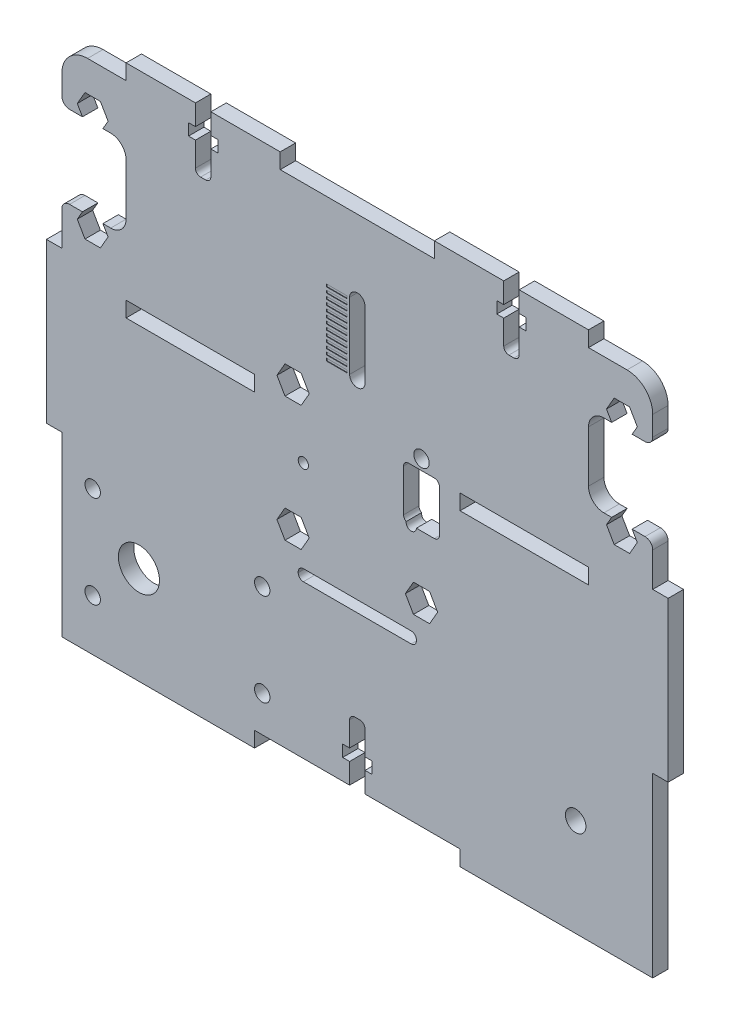
SolidWorks part; units mm, degrees
other "Marcação1"
sketch "Esboço7" plane through (-68, 31.5, 3) normal (-0.6758, 0.2828, 0.6807) x (0.7271, 0.1043, 0.6785)
sketch "Esboço8" plane through (-68, 31.5, 3) normal (-0.6758, 0.2828, 0.6807) x (0.7271, 0.1043, 0.6785)
sketch "Esboço9" plane through (-68, 31.5, 3) normal (-0.6758, 0.2828, 0.6807) x (0.7271, 0.1043, 0.6785)
sketch "Esboço10" plane through (-68, 31.5, 3) normal (-0.6758, 0.2828, 0.6807) x (0.7271, 0.1043, 0.6785)
sketch "Esboço11" plane through (-68, 36.25, 3) normal (-0.6758, 0.2828, 0.6807) x (0.7271, 0.1043, 0.6785)
sketch "Esboço13" plane through (-68, 36.25, 3) normal (-0.6758, 0.2828, 0.6807) x (0.7271, 0.1043, 0.6785)
sketch "Esboço15" plane through (-68, 36.25, 3) normal (-0.6758, 0.2828, 0.6807) x (0.7271, 0.1043, 0.6785)
sketch "Esboço19" plane through (-68, 66.25, 3) normal (-0.6758, 0.2828, 0.6807) x (0.7271, 0.1043, 0.6785)
sketch "Esboço22" plane through (-68, 95.5577, 3) normal (-0.6758, 0.2828, 0.6807) x (0.7271, 0.1043, 0.6785)
sketch "Sketch18" plane through (-60.5, 53, 1.5) normal (-0.6758, 0.2828, 0.6807) x (0.7271, 0.1043, 0.6785)
sketch "Sketch19" plane through (-60.5, 53, 1.5) normal (-0.6758, 0.2828, 0.6807) x (0.7271, 0.1043, 0.6785)
sketch "Sketch21" plane through (-60.5, 53, 1.5) normal (-0.6758, 0.2828, 0.6807) x (0.7271, 0.1043, 0.6785)
sketch "Sketch22" plane through (-60.5, 53, 1.5) normal (-0.6758, 0.2828, 0.6807) x (0.7271, 0.1043, 0.6785)
sketch "Sketch23" plane through (-60.5, 53, 1.5) normal (-0.6758, 0.2828, 0.6807) x (0.7271, 0.1043, 0.6785)
material "Acrylic (Medium-high impact)"
ref_plane "Plano frontal" through (0, 0, 0) normal (0, 0, 1) x (1, 0, 0)
ref_plane "Plano superior" through (0, 0, 0) normal (0, 1, 0) x (1, 0, 0)
ref_plane "Plano direito" through (0, 0, 0) normal (1, 0, 0) x (0, 0, -1)
sketch "Esboço1" plane through (0, 0, 0) normal (0, 0, 1) x (1, 0, 0)
  line L6 (57.5, -50) -> (-57.5, -50)
  line L8 (57.5, -50) -> (57.5, 50)
  line L9 (57.5, 50) -> (-57.5, 50)
  line L10 (-57.5, -50) -> (-57.5, 50)
  line L11 (57.5, -50) -> (-57.5, 50) construction
  line L12 (57.5, 50) -> (-57.5, -50) construction
  point P0 (0, 0)
  dimension "D1" = 100
  dimension "D2" = 115
extrude "Ressalto-extrusão1" add sketch "Esboço1" along normal mid plane 3
sketch "Esboço2" plane through (0, 0, 1.5) normal (0, 0, 1) x (1, 0, 0)
  line L1 (-20, -50) -> (20, -50)
  line L2 (-20, -50) -> (-20, -47)
  line L3 (-20, -47) -> (20, -47)
  line L4 (20, -50) -> (20, -47)
  line L6 (-57.5, -50) -> (57.5, -50) construction
  line L25 (57.5, 50) -> (-57.5, 50) construction
  line L26 (-45, 13) -> (-20, 13)
  line L29 (-45, 13) -> (-45, 10)
  line L30 (-45, 10) -> (-20, 10)
  line L31 (-20, 13) -> (-20, 10)
  line L32 (0, -1.65) -> (0, 1.65) construction
  line L33 (20, 13) -> (20, 10)
  line L34 (45, 10) -> (20, 10)
  line L35 (45, 13) -> (45, 10)
  line L36 (45, 13) -> (20, 13)
  point P6 (0, -47)
  dimension "D4" = 3
  dimension "D5" = 40
  dimension "D1" = 37
  dimension "D2" = 40
  dimension "D3" = 25
extrude "Corte-extrusão1" cut sketch "Esboço2" against normal through all
sketch "Esboço3" plane through (0, 0, 1.5) normal (0, 0, 1) x (1, 0, 0)
  line L0 (57.5, -50) -> (57.5, 50) construction
  line L1 (57.5, 15.5) -> (60.5, 15.5)
  line L2 (57.5, 15.5) -> (57.5, -15.5)
  line L3 (57.5, -15.5) -> (60.5, -15.5)
  line L4 (60.5, 15.5) -> (60.5, -15.5)
  line L5 (0, -1.65) -> (0, 1.65) construction
  line L6 (-57.5, -15.5) -> (-60.5, -15.5)
  line L7 (-57.5, 15.5) -> (-60.5, 15.5)
  line L8 (-57.5, 15.5) -> (-57.5, -15.5)
  line L9 (-60.5, 15.5) -> (-60.5, -15.5)
  line L10 (57.5, 50) -> (-57.5, 50) construction
  line L11 (-45, 53) -> (-15, 53)
  line L12 (-45, 53) -> (-45, 50)
  line L13 (-45, 50) -> (-15, 50)
  line L14 (-15, 53) -> (-15, 50)
  line L15 (15, 53) -> (15, 50)
  line L16 (45, 50) -> (15, 50)
  line L17 (45, 53) -> (45, 50)
  line L18 (45, 53) -> (15, 53)
  line L19 (0, -37.5) -> (0, 37.5) construction
  line L20 (-57.5, 50) -> (-57.5, -50) construction
  point P6 (57.5, 0)
  point P28 (0, 0)
  dimension "D1" = 3
  dimension "D2" = 31
  dimension "D3" = 3
  dimension "D4" = 30
  dimension "D5" = 12.5
  dimension "D6" = 15
extrude "Ressalto-extrusão2" add sketch "Esboço3" against normal through all
sketch "Esboço30" plane through (0, 0, -1.5) normal (0, 0, -1) x (-1, 0, 0)
  line L0 (60.5, 15.5) -> (60.5, -15.5) construction
  line L1 (57.5, -50) -> (20, -50) construction
  circle A0 centre (42.5, -31) radius 4
  dimension "D1" = 8
  dimension "D2" = 18
  dimension "D3" = 19
extrude "Corte-extrusão11" cut sketch "Esboço30" against normal through all both and the other way through all
sketch "Esboço31" plane through (0, 0, -1.5) normal (0, 0, -1) x (-1, 0, 0)
  circle A4 centre (51.5, -22) radius 1.5
  circle A5 centre (51.5, -40) radius 1.5
  circle A6 centre (42.5, -31) radius 4 construction
  circle A7 centre (18.5, -22) radius 1.5
  circle A8 centre (18.5, -40) radius 1.5
  dimension "D1" = 3
  dimension "D2" = 9
  dimension "D3" = 9
  dimension "D4" = 18
  dimension "D5" = 33
extrude "Corte-extrusão12" cut sketch "Esboço31" against normal through all both and the other way through all
sketch "Esboço4" plane through (0, 0, 1.5) normal (0, 0, 1) x (1, 0, 0)
  line L0 (-46.5, -31) -> (-38.5, -31) construction
  line L61 (-57.5, -15.5) -> (-57.5, -50) construction
  line L65 (57.5, -50) -> (57.5, -15.5) construction
  circle A9 centre (-42.5, -31) radius 4 construction
  circle A13 centre (42.5, -31) radius 2
  point P70 (-42.5, -31)
  dimension "D1" = 15
  dimension "D2" = 4
  dimension "D8" = 15
extrude "Corte-extrusão2" cut sketch "Esboço4" against normal through all
sketch "Sketch5" plane through (0, 0, 0) normal (0, 0, 1) x (1, 0, 0)
  line L0 (20, -47) -> (-20, -47) construction
  line L1 (-1.5, -47) -> (1.5, -47)
  line L2 (-1.5, -47) -> (-1.5, -43)
  line L3 (-0.5, -35) -> (0.5, -35)
  line L4 (1.5, -47) -> (1.5, -43)
  line L5 (1.5, -40.73) -> (2.85, -40.73)
  line L6 (-2.85, -40.73) -> (-1.5, -40.73)
  line L7 (-2.85, -40.73) -> (-2.85, -43)
  line L8 (-2.85, -43) -> (-1.5, -43)
  line L9 (2.85, -40.73) -> (2.85, -43)
  line L10 (-1.5, -40.73) -> (-1.5, -36)
  line L11 (1.5, -43) -> (2.85, -43)
  line L12 (1.5, -40.73) -> (1.5, -36)
  arc A0 (0.5, -35) -> (1.5, -36) centre (0.5, -36) cw
  arc A1 (-1.5, -36) -> (-0.5, -35) centre (-0.5, -36) cw
  point P6 (0, -35)
  point P18 (1.5, -35)
  point P21 (-1.5, -35)
  dimension "D7" = 1
  dimension "D1" = 12
  dimension "D2" = 3
  dimension "D3" = 2.27
  dimension "D4" = 1.35
  dimension "D5" = 1.35
  dimension "D6" = 4
extrude "Cut-Extrude2" cut sketch "Sketch5" against normal through all both and the other way through all
sketch "Sketch8" plane through (0, 0, 1.5) normal (0, 0, 1) x (1, 0, 0)
  line L8 (-57.5, 39.6519) -> (-53.4896, 39.6519)
  line L9 (-58, 31.6519) -> (-58, 23.6519) construction
  line L10 (-57.5, 23.6519) -> (-53.4896, 23.6519)
  line L11 (-45, 36.6519) -> (-45, 26.6519)
  line L12 (-58, 31.6519) -> (-45, 31.6519) construction
  line L13 (-48.5, 41.4019) -> (-50, 44)
  line L14 (-50, 44) -> (-53, 44)
  line L15 (-53, 44) -> (-54.5, 41.4019)
  line L16 (-54.5, 41.4019) -> (-53.4896, 39.6519)
  line L18 (-49.5104, 39.6519) -> (-48.5, 41.4019)
  line L19 (-49.5104, 39.6519) -> (-48, 39.6519)
  line L22 (-53.8581, 38.8038) -> (-52.2318, 38.8038) [skipped]
  line L24 (-49.5104, 23.6519) -> (-48.5, 21.9019)
  line L25 (-54.5, 21.9019) -> (-53.4896, 23.6519)
  line L26 (-53, 19.3038) -> (-54.5, 21.9019)
  line L27 (-50, 19.3038) -> (-53, 19.3038)
  line L28 (-48.5, 21.9019) -> (-50, 19.3038)
  line L29 (-45, 50) -> (-57.5, 50) construction
  line L30 (-57.5, 50) -> (-57.5, 15.5) construction
  line L31 (-57.5, 39.6519) -> (-57.5, 23.6519)
  line L32 (-58, 39.6519) -> (-58, 31.6519) construction
  line L33 (-58, 39.6519) -> (-57.5, 39.6519) construction
  line L34 (-58, 23.6519) -> (-57.5, 23.6519) construction
  line L35 (-49.5104, 23.6519) -> (-48, 23.6519)
  line L36 (0, -1.65) -> (0, 1.65) construction
  line L37 (58, 23.6519) -> (57.5, 23.6519) construction
  line L38 (58, 39.6519) -> (57.5, 39.6519) construction
  line L39 (58, 39.6519) -> (58, 31.6519) construction
  line L40 (58, 31.6519) -> (45, 31.6519) construction
  line L41 (58, 31.6519) -> (58, 23.6519) construction
  line L42 (49.5104, 23.6519) -> (48, 23.6519)
  line L43 (57.5, 39.6519) -> (57.5, 23.6519)
  line L44 (48.5, 21.9019) -> (50, 19.3038)
  line L45 (50, 19.3038) -> (53, 19.3038)
  line L46 (53, 19.3038) -> (54.5, 21.9019)
  line L47 (54.5, 21.9019) -> (53.4896, 23.6519)
  line L48 (49.5104, 23.6519) -> (48.5, 21.9019)
  line L49 (49.5104, 39.6519) -> (48, 39.6519)
  line L50 (49.5104, 39.6519) -> (48.5, 41.4019)
  line L51 (54.5, 41.4019) -> (53.4896, 39.6519)
  line L52 (53, 44) -> (54.5, 41.4019)
  line L53 (50, 44) -> (53, 44)
  line L54 (48.5, 41.4019) -> (50, 44)
  line L55 (45, 36.6519) -> (45, 26.6519)
  line L56 (57.5, 23.6519) -> (53.4896, 23.6519)
  line L57 (57.5, 39.6519) -> (53.4896, 39.6519)
  arc A0 (-49.25, 40.1029) -> (-53.75, 40.1029) centre (-51.5, 41.4019) ccw construction
  arc A1 (-49.25, 23.201) -> (-53.75, 23.201) centre (-51.5, 21.9019) cw construction
  arc A2 (-48, 23.6519) -> (-45, 26.6519) centre (-48, 26.6519) ccw
  arc A3 (-48, 39.6519) -> (-45, 36.6519) centre (-48, 36.6519) cw
  arc A4 (49.25, 23.201) -> (53.75, 23.201) centre (51.5, 21.9019) ccw construction
  arc A5 (49.25, 40.1029) -> (53.75, 40.1029) centre (51.5, 41.4019) cw construction
  arc A6 (48, 39.6519) -> (45, 36.6519) centre (48, 36.6519) ccw
  arc A7 (48, 23.6519) -> (45, 26.6519) centre (48, 26.6519) cw
  point P27 (-51.5, 31.6519)
  point P36 (-45, 23.6519)
  point P39 (-45, 39.6519)
  point P72 (45, 39.6519)
  point P73 (45, 23.6519)
  dimension "D1" = 13
  dimension "D3" = 3
  dimension "D5" = 6
  dimension "D4" = 19.5
  dimension "D6" = 3
  dimension "D7" = 3
  dimension "D8" = 16
extrude "Cut-Extrude6" cut sketch "Sketch8" against normal through all both and the other way through all
fillet "Fillet2" radius 1.5 4 edges at (57.5, 39.6519, 0) (57.5, 23.6519, 0) (-57.5, 23.6519, 0) (-57.5, 39.6519, 0)
sketch "Sketch17" plane through (0, 0, 0) normal (0, 0, 1) x (1, 0, 0)
  line L1 (-54.5, 33.7) -> (-43, 33.7)
  line L2 (-54.5, 33.7) -> (-54.5, 30.7)
  line L3 (-54.5, 30.7) -> (-43, 30.7)
  line L4 (-43, 33.7) -> (-43, 30.7)
  line L5 (-45, 50) -> (-57.5, 50) construction
  line L6 (-57.5, 50) -> (-57.5, 41.1519) construction
  line L7 (0, -1.65) -> (0, 1.65) construction
  line L8 (43, 33.7) -> (43, 30.7)
  line L9 (54.5, 30.7) -> (43, 30.7)
  line L10 (54.5, 33.7) -> (54.5, 30.7)
  line L11 (54.5, 33.7) -> (43, 33.7)
  circle A0 centre (-51.25, 41.5) radius 1.5
  circle A1 centre (46.25, 41.5) radius 1.5
  point P6 (-48.75, 33.7)
  point P20 (48.75, 33.7)
  dimension "D2" = 3
  dimension "D5" = 7.8
  dimension "D6" = 7
  dimension "D1" = 11.5
  dimension "D3" = 3
  dimension "D4" = 2.5
  dimension "D7" = 3
  dimension "D8" = 2.5
  dimension "D9" = 86
extrude "Corte Gy-53LDK" [suppressed] cut sketch "Sketch17" against normal through all both and the other way through all
sketch "Sketch11" plane through (0, 0, 0) normal (0, 0, 1) x (1, 0, 0)
  line L0 (-15, 53) -> (-45, 53) construction
  line L1 (-31.5, 53) -> (-28.5, 53)
  line L2 (-31.5, 53) -> (-31.5, 49)
  line L3 (-30.5, 41) -> (-29.5, 41)
  line L4 (-28.5, 53) -> (-28.5, 49)
  line L5 (-45, 53) -> (-45, 50) construction
  line L6 (-28.5, 49) -> (-27.15, 49)
  line L7 (-32.85, 49) -> (-31.5, 49)
  line L8 (-32.85, 49) -> (-32.85, 46.73)
  line L9 (-32.85, 46.73) -> (-31.5, 46.73)
  line L10 (-27.15, 49) -> (-27.15, 46.73)
  line L11 (-31.5, 46.73) -> (-31.5, 42)
  line L12 (-28.5, 46.73) -> (-28.5, 42)
  line L13 (-28.5, 46.73) -> (-27.15, 46.73)
  line L14 (0, -1.65) -> (0, 1.65) construction
  line L15 (28.5, 46.73) -> (27.15, 46.73)
  line L16 (28.5, 46.73) -> (28.5, 42)
  line L17 (31.5, 46.73) -> (31.5, 42)
  line L18 (27.15, 49) -> (27.15, 46.73)
  line L19 (32.85, 46.73) -> (31.5, 46.73)
  line L20 (32.85, 49) -> (32.85, 46.73)
  line L21 (32.85, 49) -> (31.5, 49)
  line L22 (28.5, 49) -> (27.15, 49)
  line L23 (28.5, 53) -> (28.5, 49)
  line L24 (30.5, 41) -> (29.5, 41)
  line L25 (31.5, 53) -> (31.5, 49)
  line L26 (31.5, 53) -> (28.5, 53)
  arc A0 (-29.5, 41) -> (-28.5, 42) centre (-29.5, 42) ccw
  arc A1 (-31.5, 42) -> (-30.5, 41) centre (-30.5, 42) ccw
  arc A2 (31.5, 42) -> (30.5, 41) centre (30.5, 42) cw
  arc A3 (29.5, 41) -> (28.5, 42) centre (29.5, 42) cw
  point P12 (-31.5, 41)
  point P39 (31.5, 41)
  dimension "D4" = 1
  dimension "D1" = 3
  dimension "D2" = 12
  dimension "D3" = 13.5
  dimension "D5" = 4
  dimension "D6" = 2.27
  dimension "D7" = 1.35
  dimension "D8" = 1.35
extrude "Cut-Extrude8" cut sketch "Sketch11" against normal through all both and the other way through all
sketch "Sketch16" plane through (0, 0, 0) normal (0, 0, 1) x (1, 0, 0)
  line L3 (15.64, -9.2807) -> (14.07, -6.5614)
  line L4 (10, 13.0193) -> (15, 13.0193)
  line L5 (9, 12.0193) -> (9, 3.8193)
  line L6 (10, 2.8193) -> (15, 2.8193)
  line L7 (16, 12.0193) -> (16, 3.8193)
  line L8 (14.07, -6.5614) -> (10.93, -6.5614)
  line L9 (10.93, -6.5614) -> (9.36, -9.2807)
  line L10 (9.36, -9.2807) -> (10.93, -12)
  line L11 (10.93, -12) -> (14.07, -12)
  line L12 (14.07, -12) -> (15.64, -9.2807)
  line L14 (-9.36, 15.0193) -> (-10.93, 17.7386)
  line L15 (-10.93, 17.7386) -> (-14.07, 17.7386)
  line L16 (-14.07, 17.7386) -> (-15.64, 15.0193)
  line L17 (-15.64, 15.0193) -> (-14.07, 12.3)
  line L18 (-14.07, 12.3) -> (-10.93, 12.3)
  line L19 (-10.93, 12.3) -> (-9.36, 15.0193)
  line L20 (-9.36, -9.2807) -> (-10.93, -6.5614)
  line L21 (-10.93, -6.5614) -> (-14.07, -6.5614)
  line L22 (-14.07, -6.5614) -> (-15.64, -9.2807)
  line L23 (-15.64, -9.2807) -> (-14.07, -12)
  line L24 (-14.07, -12) -> (-10.93, -12)
  line L25 (-10.93, -12) -> (-9.36, -9.2807)
  line L26 (-12.5, 15.0193) -> (12.5, 15.0193) construction
  line L27 (15, 50) -> (-15, 50) construction
  circle A0 centre (-12.5, 15.0193) radius 1.5 construction
  circle A1 centre (12.5, 15.0193) radius 1.5
  circle A2 centre (-12.5, -9.2807) radius 1.5 construction
  circle A3 centre (12.5, -9.2807) radius 1.5 construction
  arc A4 (9, 3.8193) -> (10, 2.8193) centre (10, 3.8193) ccw
  arc A5 (15, 2.8193) -> (16, 3.8193) centre (15, 3.8193) ccw
  arc A6 (15, 13.0193) -> (16, 12.0193) centre (15, 12.0193) cw
  arc A7 (10, 13.0193) -> (9, 12.0193) centre (10, 12.0193) ccw
  circle A8 centre (12.5, -9.2807) radius 2.7193 construction
  circle A9 centre (-12.5, 15.0193) radius 2.7193 construction
  circle A10 centre (-12.5, -9.2807) radius 2.7193 construction
  circle A11 centre (-18.5, -22) radius 1.5 construction
  point P8 (12.5, 13.0193)
  point P14 (0, 15.0193)
  point P21 (16, 2.8193)
  point P24 (16, 13.0193)
  dimension "D1" = 3
  dimension "D2" = 25
  dimension "D3" = 24.3
  dimension "D4" = 8.5
  dimension "D7" = 2
  dimension "D9" = 1
  dimension "D6" = 0.5
  dimension "D8" = 10.2
  dimension "D10" = 3.14
  dimension "D11" = 3.14
  dimension "D12" = 3.14
extrude "Cut-Extrude12" cut sketch "Sketch16" against normal through all both and the other way through all
sketch "Esboço32" plane through (0, 0, 0) normal (0, 0, 1) x (1, 0, 0)
  line L0 (0, -1.65) -> (0, 1.65) construction
  line L1 (-14.07, -12) -> (-10.93, -12) construction
  line L2 (-10.5, -15) -> (10.5, -15)
  line L3 (-11.5, -16) -> (-11.5, -16.2)
  line L4 (-10.5, -17.2) -> (10.5, -17.2)
  line L5 (11.5, -16) -> (11.5, -16.2)
  circle A0 centre (-10.5, 2.82) radius 1
  circle A1 centre (10.5, 2.82) radius 1
  arc A2 (10.5, -17.2) -> (11.5, -16.2) centre (10.5, -16.2) ccw
  arc A3 (10.5, -15) -> (11.5, -16) centre (10.5, -16) cw
  arc A4 (-11.5, -16.2) -> (-10.5, -17.2) centre (-10.5, -16.2) ccw
  arc A5 (-10.5, -15) -> (-11.5, -16) centre (-10.5, -16) ccw
  point P11 (0, -15)
  point P16 (11.5, -17.2)
  point P19 (11.5, -15)
  dimension "D1" = 2
  dimension "D2" = 2.82
  dimension "D3" = 21
  dimension "D6" = 1
  dimension "D4" = 3
  dimension "D5" = 2.2
  dimension "D7" = 23
extrude "Corte-extrusão13" cut sketch "Esboço32" against normal through all both and the other way through all
sketch "Sketch12" plane through (0, 0, 1.5) normal (0, 0, 1) x (1, 0, 0)
  line L2 (-6, 23.7803) -> (-2, 23.7803)
  line L4 (0, 22.2386) -> (0, 35.2386) construction
  line L7 (-1.5, 22.2386) -> (-1.5, 35.2386)
  line L8 (1.5, 22.2386) -> (1.5, 35.2386)
  line L9 (-6, 22.7386) -> (-2, 22.7386)
  line L10 (-6, 22.7386) -> (-6, 22.2386)
  line L11 (-6, 22.2386) -> (-2, 22.2386)
  line L12 (-2, 22.7386) -> (-2, 22.2386)
  line L13 (-6, 23.7803) -> (-6, 23.2803)
  line L14 (-6, 23.2803) -> (-2, 23.2803)
  line L15 (-2, 23.7803) -> (-2, 23.2803)
  line L16 (-6, 24.822) -> (-2, 24.822)
  line L17 (-6, 24.822) -> (-6, 24.322)
  line L18 (-6, 24.322) -> (-2, 24.322)
  line L19 (-2, 24.822) -> (-2, 24.322)
  line L20 (-6, 25.8636) -> (-2, 25.8636)
  line L21 (-6, 25.8636) -> (-6, 25.3636)
  line L22 (-6, 25.3636) -> (-2, 25.3636)
  line L23 (-2, 25.8636) -> (-2, 25.3636)
  line L24 (-6, 26.9053) -> (-2, 26.9053)
  line L25 (-6, 26.9053) -> (-6, 26.4053)
  line L26 (-6, 26.4053) -> (-2, 26.4053)
  line L27 (-2, 26.9053) -> (-2, 26.4053)
  line L28 (-6, 27.947) -> (-2, 27.947)
  line L29 (-6, 27.947) -> (-6, 27.447)
  line L30 (-6, 27.447) -> (-2, 27.447)
  line L31 (-2, 27.947) -> (-2, 27.447)
  line L32 (-6, 28.9886) -> (-2, 28.9886)
  line L33 (-6, 28.9886) -> (-6, 28.4886)
  line L34 (-6, 28.4886) -> (-2, 28.4886)
  line L35 (-2, 28.9886) -> (-2, 28.4886)
  line L36 (-6, 30.0303) -> (-2, 30.0303)
  line L37 (-6, 30.0303) -> (-6, 29.5303)
  line L38 (-6, 29.5303) -> (-2, 29.5303)
  line L39 (-2, 30.0303) -> (-2, 29.5303)
  line L40 (-6, 31.072) -> (-2, 31.072)
  line L41 (-6, 31.072) -> (-6, 30.572)
  line L42 (-6, 30.572) -> (-2, 30.572)
  line L43 (-2, 31.072) -> (-2, 30.572)
  line L44 (-6, 32.1136) -> (-2, 32.1136)
  line L45 (-6, 32.1136) -> (-6, 31.6136)
  line L46 (-6, 31.6136) -> (-2, 31.6136)
  line L47 (-2, 32.1136) -> (-2, 31.6136)
  line L48 (-6, 33.1553) -> (-2, 33.1553)
  line L49 (-6, 33.1553) -> (-6, 32.6553)
  line L50 (-6, 32.6553) -> (-2, 32.6553)
  line L51 (-2, 33.1553) -> (-2, 32.6553)
  line L52 (-6, 34.197) -> (-2, 34.197)
  line L53 (-6, 34.197) -> (-6, 33.697)
  line L54 (-6, 33.697) -> (-2, 33.697)
  line L55 (-2, 34.197) -> (-2, 33.697)
  line L56 (-6, 35.2386) -> (-2, 35.2386)
  line L57 (-6, 35.2386) -> (-6, 34.7386)
  line L58 (-6, 34.7386) -> (-2, 34.7386)
  line L59 (-2, 35.2386) -> (-2, 34.7386)
  line L61 (-10.93, 17.7386) -> (-14.07, 17.7386) construction
  circle A1 centre (0, 22.2386) radius 1.5 construction
  arc A4 (-1.5, 22.2386) -> (1.5, 22.2386) centre (0, 22.2386) ccw
  arc A5 (1.5, 35.2386) -> (-1.5, 35.2386) centre (0, 35.2386) ccw
  point P6 (0, 28.7386)
  dimension "D1" = 3
  dimension "D2" = 3
  dimension "D3" = 13
  dimension "D4" = 0.5
  dimension "D5" = 4
  dimension "D6" = 0.5
  dimension "D7" = 13
extrude "Cut-Extrude9" cut sketch "Sketch12" against normal through all contours L8 A5 L7 A4 | A5 L8 A4 L7 region at (0, 28.7386, 1.5)
fillet "Fillet1" radius 5 2 edges at (-57.5, 50, 0) (57.5, 50, 0)
extrude "Cut-Extrude13" cut sketch "Sketch12<4>" against normal blind 0.1 contours L52 L55 L54 L53 | L48 L51 L50 L49 | L40 L43 L42 L41 | L36 L39 L38 L37 | L24 L27 L26 L25 | L16 L19 L18 L17 | L59 L56 L57 L58 | L55 L52 L53 L54 | L51 L48 L49 L50 | L47 L44 L45 L46 | L43 L40 L41 L42 | L39 L36 L37 L38 | L35 L32 L33 L34 | L31 L28 L29 L30 | L27 L24 L25 L26 | L23 L20 L21 L22 | L19 L16 L17 L18 | L15 L2 L13 L14 | L12 L9 L10 L11 region at (-4, 23.5303, 1.5) region at (-4, 22.4886, 1.5) region at (-4, 24.572, 1.5) region at (-4, 25.6136, 1.5) region at (-4, 26.6553, 1.5) region at (-4, 27.697, 1.5) region at (-4, 28.7386, 1.5) region at (-4, 29.7803, 1.5) region at (-4, 30.822, 1.5) region at (-4, 31.8636, 1.5) region at (-4, 32.9053, 1.5) region at (-4, 33.947, 1.5) region at (-4, 34.9886, 1.5)
sketch "Sketch12<4>" plane through (0, 0, 1.5) normal (0, 0, 1) x (1, 0, 0) same geometry as "Sketch12"
